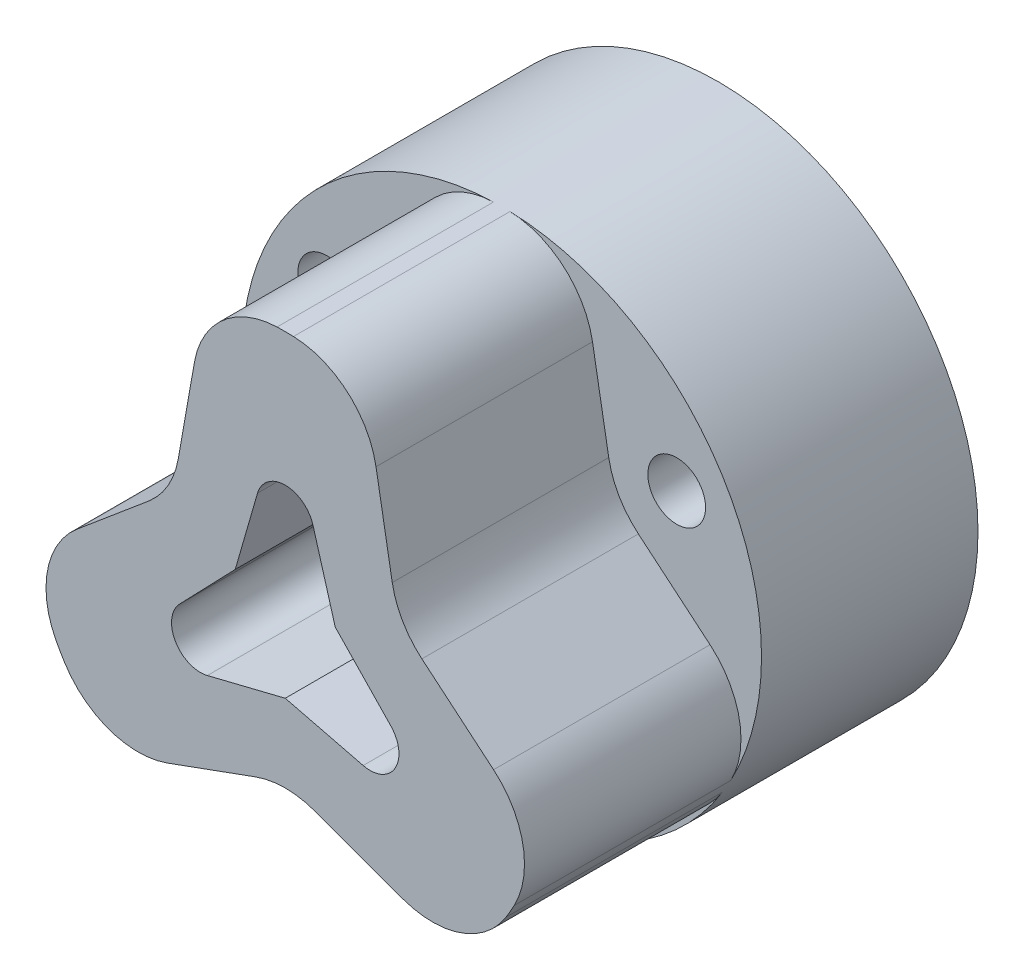
SolidWorks part; units mm, degrees
material "ABS"
ref_plane "Front Plane" through (0, 0, 0) normal (0, 0, 1) x (1, 0, 0)
ref_plane "Top Plane" through (0, 0, 0) normal (0, 1, 0) x (1, 0, 0)
ref_plane "Right Plane" through (0, 0, 0) normal (1, 0, 0) x (0, 0, -1)
sketch "Sketch1" plane through (0, 0, 0) normal (0, 0, 1) x (1, 0, 0)
  circle A0 centre (0, 0) radius 18
  dimension "D1" = 36
extrude "Boss-Extrude1" add sketch "Sketch1" along normal blind 30
sketch "Sketch2" plane through (0, 0, 0) normal (0, 0, -1) x (-1, 0, 0)
  line L0 (0, 0) -> (0, 19.7501) construction
  line L1 (0, 0) -> (12.1244, 7) construction
  circle A0 centre (12.1244, 7) radius 2
  dimension "D2" = 4
  dimension "D1" = 60
  dimension "D3" = 14
extrude "Cut-Extrude1" cut sketch "Sketch2" against normal blind 40
ref_axis "Axis1" through (0, 0, 30) along (0, 0, -1)
sketch "Sketch3" plane through (0, 0, 30) normal (0, 0, 1) x (1, 0, 0)
  line L0 (-12.1244, 7) -> (0, 0) construction
  line L1 (0, 0) -> (0, 13.3417) construction
  line L2 (-14.6244, 2.6699) -> (-20.6865, 6.1699) construction
  line L3 (-9.6244, 11.3301) -> (-15.6865, 14.8301) construction
  line L4 (-15.6865, 14.8301) -> (-20.6865, 6.1699)
  line L5 (-7.7942, 4.5) -> (-5.5696, 17.1167)
  line L6 (-7.7942, 4.5) -> (-17.6082, -3.7349)
  line L7 (-20.6865, 6.1699) -> (-17.6082, -3.7349)
  line L8 (-15.6865, 14.8301) -> (-5.5696, 17.1167)
  arc A0 (-14.6244, 2.6699) -> (-9.6244, 11.3301) centre (-12.1244, 7) ccw construction
  circle A1 centre (0, 0) radius 18 construction
  dimension "D1" = 10
  dimension "D2" = 60
  dimension "D3" = 14
  dimension "D4" = 7
  dimension "D5" = 70
  dimension "D6" = 70
extrude "Cut-Extrude2" cut sketch "Sketch3" against normal blind 15
fillet "Fillet2" radius 6 3 edges at (-7.7942, 4.5, 22.5) (-17.6082, -3.7349, 22.5) (-5.5696, 17.1167, 22.5)
pattern_circular "CirPattern3" count 3 over 360 about axis through (0, 0, 30) along (0, 0, -1) of "Cut-Extrude2", "Fillet2", "Cut-Extrude1"
sketch "Sketch4" plane through (0, 0, 30) normal (0, 0, 1) x (1, 0, 0)
  line L0 (0, 0) -> (0, 14) construction
  line L1 (0, 0) -> (-12.1244, -7) construction
  line L2 (0, 0) -> (12.1244, -7)
  line L3 (-12.1244, -7) -> (-3.4641, 2)
  line L4 (-3.4641, 2) -> (0, 14)
  line L5 (0, 14) -> (3.4641, 2)
  line L6 (0, -4) -> (12.1244, -7)
  line L7 (-12.1244, -7) -> (0, -4)
  line L8 (3.4641, 2) -> (12.1244, -7)
  circle A0 centre (0, 0) radius 14 construction
  circle A1 centre (0, 0) radius 10 construction
  circle A2 centre (0, 0) radius 4 construction
  dimension "D1" = 28
  dimension "D2" = 20
  dimension "D5" = 8
  dimension "D3" = 120
  dimension "D4" = 120
extrude "Cut-Extrude3" cut sketch "Sketch4" against normal up to vertex (30 mm away) contours L8 L5 L4 L3 L7 L6 region at (-7.5631, -2.7224, 30) up to point (0, 0, 0)
fillet "Fillet3" radius 2 3 edges at (0, 14, 15) (-12.1244, -7, 15) (12.1244, -7, 15)
